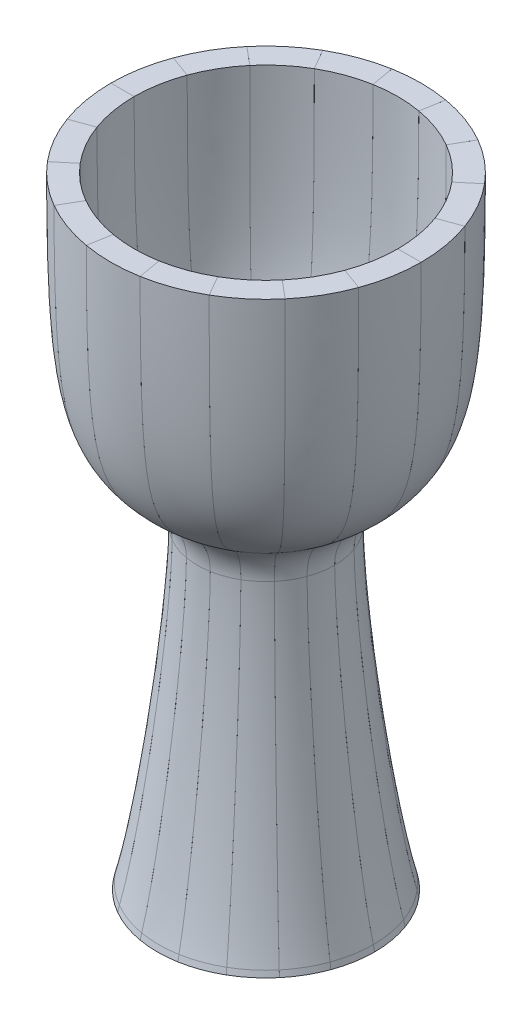
SolidWorks part; units mm, degrees
ref_plane "Front" through (0, 0, 0) normal (0, 0, 1) x (1, 0, 0)
ref_plane "Top" through (0, 0, 0) normal (0, 1, 0) x (1, 0, 0)
ref_plane "Right" through (0, 0, 0) normal (1, 0, 0) x (0, 0, -1)
sketch "Sketch1" plane through (0, 0, 0) normal (0, 0, 1) x (1, 0, 0)
  line L0 (0, 0) -> (0, 508) construction
  line L1 (0, 0) -> (88.9, 0) construction
  line L2 (0, 508) -> (127, 508) construction
  line L3 (0, 279.4) -> (57.15, 279.4) construction
  line L4 (127, 508) -> (107.95, 508)
  line L5 (88.9, 0) -> (69.356, 0)
  line L6 (87.8154, 4.7069) -> (88.9, 0)
  arc A0 (72.3812, 289.3484) -> (56.2249, 257.8623) centre (94.3234, 258.2012) ccw
  arc A1 (61.4101, 304.9221) -> (37.1757, 257.6928) centre (94.3234, 258.2012) ccw
  conic Q0 (127, 508) -> (72.3812, 289.3484) control (127, 327.8255) rho 0.652576
  conic Q1 (56.2249, 257.8623) -> (87.8154, 4.7069) control (57.4164, 123.9255) rho 0.339195
  spline S0 degree 1 poles (107.95, 508) (61.4101, 304.9221) knots 0 0 1 1 construction
  spline S1 degree 1 poles (37.1757, 257.6928) (69.356, 0) knots 0 0 1 1 construction
  spline S2 degree 3 poles (107.95, 508) (107.95, 507.131) (107.9494, 505.3811) (107.9462, 501.9768) (107.9381, 497.8303) (107.9223, 493.0391) (107.8933, 486.8767) (107.8429, 479.5781) (107.7612, 471.4008) (107.6594, 463.7487) (107.4984, 454.1811) (107.252, 443.3024) (106.8898, 431.6894) (106.4653, 421.2935) (105.981, 411.9343) (105.2582, 400.6452) (104.2128, 388.4581) (102.7333, 376.1908) (101.0236, 365.7814) (99.0732, 356.8581) (96.8635, 349.1274) (94.3595, 342.332) (91.4913, 336.2163) (88.1212, 330.5035) (84.6909, 325.8239) (81.3716, 321.9647) (78.5239, 318.9694) (75.2356, 315.8277) (72.0438, 313.0467) (69.1556, 310.6953) (66.8044, 308.8611) (64.6684, 307.2628) (62.8528, 305.945) (61.8878, 305.2586) (61.4101, 304.9221) knots 0 0 0 0 0.003906 0.007812 0.015625 0.023438 0.03125 0.046875 0.0625 0.078125 0.09375 0.125 0.15625 0.1875 0.21875 0.25 0.3125 0.375 0.4375 0.5 0.5625 0.625 0.6875 0.75 0.8125 0.84375 0.875 0.90625 0.9375 0.953125 0.96875 0.984375 0.992188 1 1 1 1
  spline S3 degree 3 poles (37.1757, 257.6928) (37.1826, 256.9153) (37.2012, 255.3882) (37.2614, 252.1098) (37.3795, 247.7365) (37.5949, 241.9803) (37.8883, 235.7154) (38.264, 228.9315) (38.8792, 219.197) (39.8707, 205.7532) (41.4289, 187.7512) (43.3483, 168.2028) (45.599, 147.5676) (48.1286, 126.4124) (50.866, 105.3597) (53.7278, 85.0255) (56.6274, 65.9585) (59.4836, 48.5907) (61.7702, 35.7746) (63.5182, 26.5832) (64.7846, 20.2225) (66.003, 14.3919) (67.1725, 9.0766) (68.1039, 5.0716) (68.8296, 2.0871) (69.1765, 0.7041) (69.356, 0) knots 0 0 0 0 0.015625 0.03125 0.0625 0.09375 0.125 0.15625 0.1875 0.25 0.3125 0.375 0.4375 0.5 0.5625 0.625 0.6875 0.75 0.8125 0.84375 0.875 0.90625 0.9375 0.96875 0.984375 1 1 1 1
  point P20 (0, 0)
  dimension "D4" = 38.1
  dimension "D1" = 508
  dimension "D2" = 88.9
  dimension "D3" = 127
  dimension "D5" = 279.4
  dimension "D6" = 19.05
revolve "Revolve1" add sketch "Sketch1" angle 360 about L0
ref_plane "Plane1" through (0, 508, 0) normal (0, 1, 0) x (1, 0, 0)
sketch "Sketch2" plane through (0, 508, 0) normal (0, 1, 0) x (1, 0, 0)
  line L0 (-18.9731, 0) -> (-18.9731, 0.0025)
  line L1 (-18.9731, 0) -> (-323.7731, 0.0204)
  line L2 (-18.9731, 0.0025) -> (-323.7731, 0.0229)
  line L3 (-323.7731, 0.0204) -> (-323.7731, 0.0229)
  line L4 (-17.8289, 6.4892) -> (-304.2403, 110.7561)
  line L5 (-304.2403, 110.7561) -> (-304.2394, 110.7585)
  line L6 (-17.8281, 6.4916) -> (-304.2394, 110.7585)
  line L7 (-17.8289, 6.4892) -> (-17.8281, 6.4916)
  line L8 (-14.5343, 12.1957) -> (-248.0115, 208.133)
  line L9 (-248.0115, 208.133) -> (-248.0099, 208.1349)
  line L10 (-14.5326, 12.1977) -> (-248.0099, 208.1349)
  line L11 (-14.5343, 12.1957) -> (-14.5326, 12.1977)
  line L12 (-9.4866, 16.4312) -> (-161.8689, 280.406)
  line L13 (-161.8689, 280.406) -> (-161.8667, 280.4072)
  line L14 (-9.4844, 16.4325) -> (-161.8667, 280.4072)
  line L15 (-9.4866, 16.4312) -> (-9.4844, 16.4325)
  line L16 (-3.2947, 18.6849) -> (-56.2025, 318.8579)
  line L17 (-56.2025, 318.8579) -> (-56.2, 318.8583)
  line L18 (-3.2922, 18.6853) -> (-56.2, 318.8583)
  line L19 (-3.2947, 18.6849) -> (-3.2922, 18.6853)
  line L20 (3.2947, 18.6849) -> (56.2427, 318.8508)
  line L21 (56.2427, 318.8508) -> (56.2452, 318.8503)
  line L22 (3.2972, 18.6845) -> (56.2452, 318.8503)
  line L23 (3.2947, 18.6849) -> (3.2972, 18.6845)
  line L24 (9.4866, 16.4312) -> (161.9042, 280.3856)
  line L25 (161.9042, 280.3856) -> (161.9064, 280.3843)
  line L26 (9.4888, 16.43) -> (161.9064, 280.3843)
  line L27 (9.4866, 16.4312) -> (9.4888, 16.43)
  line L28 (14.5343, 12.1957) -> (248.0377, 208.1017)
  line L29 (248.0377, 208.1017) -> (248.0394, 208.0998)
  line L30 (14.5359, 12.1938) -> (248.0394, 208.0998)
  line L31 (14.5343, 12.1957) -> (14.5359, 12.1938)
  line L32 (17.8289, 6.4892) -> (304.2542, 110.7178)
  line L33 (304.2542, 110.7178) -> (304.2551, 110.7154)
  line L34 (17.8298, 6.4868) -> (304.2551, 110.7154)
  line L35 (17.8289, 6.4892) -> (17.8298, 6.4868)
  line L36 (18.9731, 0) -> (323.7731, -0.0204)
  line L37 (323.7731, -0.0204) -> (323.7731, -0.0229)
  line L38 (18.9731, -0.0025) -> (323.7731, -0.0229)
  line L39 (18.9731, 0) -> (18.9731, -0.0025)
  line L40 (17.8289, -6.4892) -> (304.2403, -110.7561)
  line L41 (304.2403, -110.7561) -> (304.2394, -110.7585)
  line L42 (17.8281, -6.4916) -> (304.2394, -110.7585)
  line L43 (17.8289, -6.4892) -> (17.8281, -6.4916)
  line L44 (14.5343, -12.1957) -> (248.0115, -208.133)
  line L45 (248.0115, -208.133) -> (248.0099, -208.1349)
  line L46 (14.5326, -12.1977) -> (248.0099, -208.1349)
  line L47 (14.5343, -12.1957) -> (14.5326, -12.1977)
  line L48 (9.4866, -16.4312) -> (161.8689, -280.406)
  line L49 (161.8689, -280.406) -> (161.8667, -280.4072)
  line L50 (9.4844, -16.4325) -> (161.8667, -280.4072)
  line L51 (9.4866, -16.4312) -> (9.4844, -16.4325)
  line L52 (3.2947, -18.6849) -> (56.2025, -318.8579)
  line L53 (56.2025, -318.8579) -> (56.2, -318.8583)
  line L54 (3.2922, -18.6853) -> (56.2, -318.8583)
  line L55 (3.2947, -18.6849) -> (3.2922, -18.6853)
  line L56 (-3.2947, -18.6849) -> (-56.2427, -318.8508)
  line L57 (-56.2427, -318.8508) -> (-56.2452, -318.8503)
  line L58 (-3.2972, -18.6845) -> (-56.2452, -318.8503)
  line L59 (-3.2947, -18.6849) -> (-3.2972, -18.6845)
  line L60 (-9.4866, -16.4312) -> (-161.9042, -280.3856)
  line L61 (-161.9042, -280.3856) -> (-161.9064, -280.3843)
  line L62 (-9.4888, -16.43) -> (-161.9064, -280.3843)
  line L63 (-9.4866, -16.4312) -> (-9.4888, -16.43)
  line L64 (-14.5343, -12.1957) -> (-248.0377, -208.1017)
  line L65 (-248.0377, -208.1017) -> (-248.0394, -208.0998)
  line L66 (-14.5359, -12.1938) -> (-248.0394, -208.0998)
  line L67 (-14.5343, -12.1957) -> (-14.5359, -12.1938)
  line L68 (-17.8289, -6.4892) -> (-304.2542, -110.7178)
  line L69 (-304.2542, -110.7178) -> (-304.2551, -110.7154)
  line L70 (-17.8298, -6.4868) -> (-304.2551, -110.7154)
  line L71 (-17.8289, -6.4892) -> (-17.8298, -6.4868)
  circle A0 centre (0, 0) radius 18.9731 construction
  point P77 (0, 0)
  dimension "D1" = 0.0025
  dimension "D2" = 304.8
  dimension "D3" = 18
extrude "Cut-Extrude1" cut sketch "Sketch2" against normal through all
